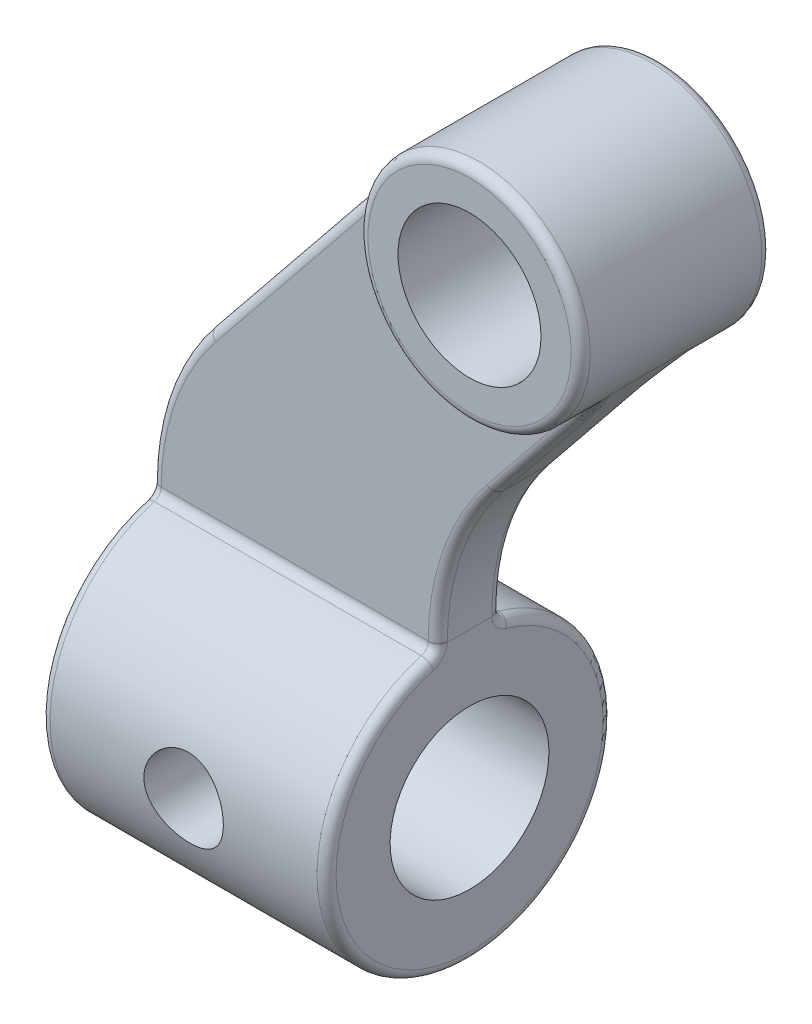
SolidWorks part; units mm, degrees
material "AISI 1020"
ref_plane "Front Plane" through (0, 0, 0) normal (0, 0, 1) x (1, 0, 0)
ref_plane "Top Plane" through (0, 0, 0) normal (0, 1, 0) x (1, 0, 0)
ref_plane "Right Plane" through (0, 0, 0) normal (1, 0, 0) x (0, 0, -1)
sketch "Sketch1" plane through (0, 0, 0) normal (0, 0, 1) x (1, 0, 0)
  line L0 (-90, 0) -> (-15, 92.8078)
  line L1 (0, 0) -> (39.4444, 48.81)
  line L2 (-17.7778, -96.141) -> (-107.7778, -96.141)
  line L3 (-107.7778, -50.2831) -> (-107.7778, -141.9989)
  line L4 (-107.7778, -141.9989) -> (-17.7778, -141.9989)
  line L5 (-17.7778, -141.9989) -> (-17.7778, -50.2831)
  line L6 (-17.7778, -50.2831) -> (-17.7778, 9.3787) construction
  line L7 (0, 0) -> (-48.2745, -59.7367) construction
  line L8 (-90, 0) -> (-130.5394, -50.165) construction
  line L9 (-107.7778, -50.2831) -> (-107.7778, 14.6425) construction
  line L10 (-107.7778, -21.9989) -> (-17.7778, -21.9989) construction
  circle A0 centre (12.2222, 70.8089) radius 35
  circle A1 centre (12.2222, 70.8089) radius 22.5
  arc A3 (0, 0) -> (-17.7778, -50.2831) centre (62.2222, -50.2831) ccw
  arc A4 (-90, 0) -> (-107.7778, -50.2831) centre (-27.7778, -50.2831) ccw
  point P4 (-107.7778, 136.1054)
  point P23 (0, 0)
  point P24 (-1077.7778, -961.4101)
  point P25 (-15, 345.4255)
  point P26 (-107.7778, 14.6425)
  point P27 (-15, 220.2228)
  point P28 (-17.7778, 9.3787)
  point P29 (-48.2745, -59.7367)
  point P30 (-287.2577, -244.0939)
  point P31 (-130.5394, -50.2831)
  dimension "D1" = 45
  dimension "D2" = 70
  dimension "D3" = 80
  dimension "D4" = 80
  dimension "D5" = 120
  dimension "D6" = 90
  dimension "D7" = 30
extrude "Boss-Extrude1" add sketch "Sketch1" along normal mid plane 20 contours L0 A4 A3 L1 A0 region at (-49.7299, -22.6753, 0)
extrude "Boss-Extrude2" add sketch "Sketch1<3>" along normal mid plane 60 contours A0 A1 region at (23.5589, 102.8739, 0)
sketch "Sketch1<3>" plane through (0, 0, 0) normal (0, 0, 1) x (1, 0, 0) same geometry as "Sketch1"
ref_plane "Plane2" through (-107.7778, 0, 0) normal (-1, 0, 0) x (0, 0, 1)
sketch "Sketch3" plane through (-107.7778, 0, 0) normal (-1, 0, 0) x (0, 0, 1)
  line L1 (10, -96.141) -> (-10, -96.141) construction
  circle A0 centre (0, -96.141) radius 45
  circle A1 centre (0, -96.141) radius 25
  point P7 (0, -96.141)
  dimension "D1" = 90
  dimension "D2" = 20
extrude "Boss-Extrude4" add sketch "Sketch3" against normal blind 90
extrude "Cut-Extrude1" cut sketch "Sketch3<2>" against normal through all contours A1
sketch "Sketch3<2>" plane through (-107.7778, 0, 0) normal (-1, 0, 0) x (0, 0, 1) same geometry as "Sketch3"
fillet "Fillet2" radius 3 3 edges at (47.2222, 70.8089, -30) (-9.7767, 43.5867, -10) (-9.7767, 43.5867, 10)
fillet "Fillet3" radius 3 1 edges at (-62.7778, -52.2662, 10)
fillet "Fillet4" radius 3 1 edges at (-62.7778, -52.2662, -10)
fillet "Fillet5" radius 3 23 edges at (-57.1508, 40.6489, 10) (-103.1443, -23.4524, 10) (-107.7778, -51.8823, 10.718) (-107.7778, -141.141, 0) (-107.7778, -51.8823, -10.718) (-57.1508, 40.6489, -10) (-103.1443, -23.4524, -10) (33.9141, 41.9666, 10.6874) (33.9141, 41.9666, -10.6874) (-20.5303, 85.9644, -10.6874) (-20.5303, 85.9644, 10.6874) (47.2222, 70.8089, 30) (15.0715, 18.65, 10) (-13.1443, -23.4524, 10) (-17.7778, -51.8823, 10.718) (-17.7778, -141.141, 0) (-17.7778, -51.8823, -10.718) (-13.1443, -23.4524, -10) (15.0715, 18.65, -10)
sketch "Sketch5" plane through (0, 0, 0) normal (0, 0, 1) x (1, 0, 0)
  line L1 (-107.7778, -141.9989) -> (-17.7778, -141.9989) construction
  line L2 (-62.7778, -50.7166) -> (-62.7778, -141.9989) construction
  circle A0 centre (-62.7778, -96.9989) radius 12.5
  point P7 (0, 0)
  dimension "D1" = 25
  dimension "D2" = 45
extrude "Cut-Extrude2" cut sketch "Sketch5" against normal through all both and the other way through all
